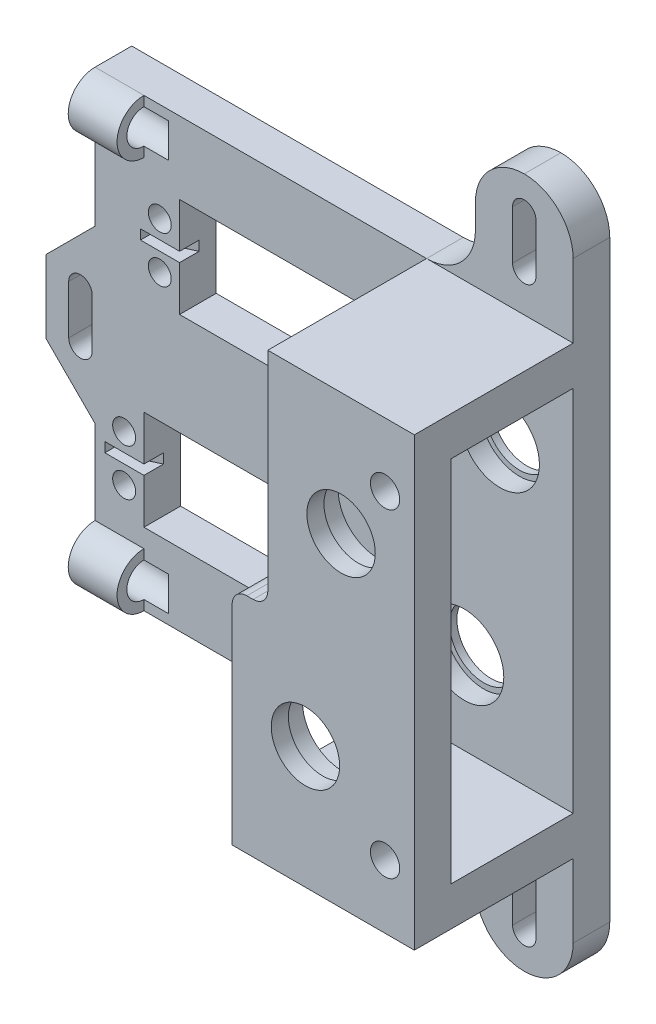
SolidWorks part; units mm, degrees
ref_plane "Front Plane" through (0, 0, 0) normal (0, 0, 1) x (1, 0, 0)
ref_plane "Top Plane" through (0, 0, 0) normal (0, 1, 0) x (1, 0, 0)
ref_plane "Right Plane" through (0, 0, 0) normal (1, 0, 0) x (0, 0, -1)
sketch "Sketch1" plane through (0, 0, 0) normal (0, 0, 1) x (1, 0, 0)
  line L0 (-15, 0) -> (22.2932, 0)
  line L5 (-15, 91.3619) -> (22.2932, 91.3619)
  line L6 (-15, 0) -> (-15, 91.3619)
  line L7 (22.2932, 0) -> (22.2932, 91.3619)
  line L8 (0, 25) -> (7.2932, 66.3619) construction
  line L9 (0, 25) -> (0, 79.2) construction
  circle A1 centre (0, 25) radius 8.1
  circle A2 centre (7.2932, 66.3619) radius 8.1
  point P4 (0, 0)
  dimension "D2" = 16.2
  dimension "D5" = 25
  dimension "D4" = 15
  dimension "D6" = 25
  dimension "D8" = 42
  dimension "D9" = 10
  dimension "D10" = 15
extrude "Boss-Extrude1" add sketch "Sketch1" along normal blind 40
ref_plane "INNER WALL" through (0, 0, 39) normal (0, 0, 1) x (1, 0, 0)
ref_plane "OUTER WALL" through (0, 0, 32.65) normal (0, 0, 1) x (1, 0, 0)
sketch "Sketch2" plane through (0, 0, 0) normal (0, 1, 0) x (1, 0, 0)
  line L1 (-15, -7.5) -> (22.2932, -7.5)
  line L2 (-15, -7.5) -> (-15, -32.5)
  line L3 (-15, -32.5) -> (22.2932, -32.5)
  line L4 (22.2932, -7.5) -> (22.2932, -32.5)
  line L6 (-15, -40) -> (-15, 0) construction
  line L7 (22.2932, -40) -> (22.2932, 0) construction
  point P9 (22.2932, -20)
  point P10 (22.2932, -20)
  dimension "D1" = 25
extrude "Cut-Extrude1" cut sketch "Sketch2" along normal through all from offset 8
sketch "Sketch10" plane through (0, 0, 40) normal (0, 0, 1) x (1, 0, 0)
  circle A0 centre (7.2932, 66.3619) radius 8.1
  circle A1 centre (0, 25) radius 10.837
  circle A2 centre (7.2932, 66.3619) radius 7
  circle A3 centre (0, 25) radius 7
  circle A4 centre (7.2932, 66.3619) radius 8.1 construction
  circle A5 centre (0, 25) radius 8.1 construction
  dimension "D2" = 14
  dimension "D4" = 14
extrude "Boss-Extrude2" add sketch "Sketch10" against normal offset from surface (3.5 mm away) 4 up to face at (-8.1, 25, 32.5)
sketch "Sketch11" plane through (0, 0, 0) normal (0, 0, -1) x (-1, 0, 0)
  circle A0 centre (-7.2932, 66.3619) radius 8.1
  circle A1 centre (-7.2932, 66.3619) radius 7
  circle A2 centre (0, 25) radius 8.1
  circle A3 centre (0, 25) radius 7
  circle A4 centre (0, 25) radius 8.1 construction
  circle A5 centre (-7.2932, 66.3619) radius 8.1 construction
  dimension "D1" = 14
  dimension "D2" = 14
extrude "Boss-Extrude3" add sketch "Sketch11" against normal offset from surface (3.5 mm away) 4 up to face at (8.1, 25, 7.5)
ref_axis "Axis1" through (0, 25, 3.5) along (0, 0, -1)
ref_plane "Plane1" through (0, 25, 0) normal (0, -1, 0) x (-1, 0, 0)
ref_axis "Axis2" through (7.2932, 66.3619, 3.5) along (0, 0, -1)
ref_plane "Plane2" through (0, 66.3619, 0) normal (0, -1, 0) x (-1, 0, 0)
sketch "Sketch12" plane through (0, 0, 0) normal (0, 0, -1) x (-1, 0, 0)
  line L0 (-20.5113, 25) -> (20.5113, 25) construction
  line L1 (15, 0) -> (75.56, 0)
  line L2 (15, 0) -> (15, 91.3619)
  line L3 (15, 91.3619) -> (75.56, 91.3619)
  line L5 (-20.5113, 66.3619) -> (20.5113, 66.3619) construction
  line L6 (24.66, 35.2) -> (65.56, 35.2)
  line L7 (24.66, 35.2) -> (24.66, 14.8)
  line L8 (24.66, 14.8) -> (65.56, 14.8)
  line L9 (65.56, 35.2) -> (65.56, 14.8)
  line L10 (-22.2932, 91.3619) -> (15, 91.3619) construction
  line L11 (17.3668, 76.5619) -> (58.2668, 76.5619)
  line L12 (17.3668, 76.5619) -> (17.3668, 56.1619)
  line L13 (17.3668, 56.1619) -> (58.2668, 56.1619)
  line L14 (58.2668, 76.5619) -> (58.2668, 56.1619)
  line L16 (15, 0) -> (-22.2932, 0) construction
  line L17 (15, 91.3619) -> (15, 0) construction
  line L20 (75.56, 91.3619) -> (75.56, 0)
  line L21 (58.2668, 56.1619) -> (58.2668, 35.2) construction
  line L22 (45.11, 35.2) -> (45.11, 14.8) construction
  line L32 (37.8168, 76.5619) -> (37.8168, 56.1619) construction
  circle A0 centre (35, 25) radius 6.6 construction
  circle A1 centre (0, 25) radius 7 construction
  circle A2 centre (27.7068, 66.3619) radius 6.6 construction
  circle A3 centre (-7.2932, 66.3619) radius 7 construction
  point P15 (45.11, 14.8)
  point P27 (17.3668, 66.3619)
  point P34 (37.8168, 56.1619)
  point P53 (45.11, 25)
  dimension "D7" = 13.2
  dimension "D11" = 13.2
  dimension "D2" = 20.4
  dimension "D3" = 40.9
  dimension "D4" = 10.11
  dimension "D9" = 10.11
  dimension "D5" = 35
  dimension "D6" = 10
extrude "Boss-Extrude4" add sketch "Sketch12" against normal up to surface (7.5 mm away) up to face at (8.1, 25, 7.5)
sketch "Sketch13" plane through (0, 0, 0) normal (0, 0, -1) x (-1, 0, 0)
  line L0 (24.66, 35.2) -> (24.66, 14.8) construction
  line L1 (-20.5113, 25) -> (20.5113, 25) construction
  line L2 (65.56, 14.8) -> (65.56, 35.2) construction
  line L3 (17.3668, 76.5619) -> (17.3668, 56.1619) construction
  line L5 (-20.5113, 66.3619) -> (20.5113, 66.3619) construction
  line L6 (58.2668, 56.1619) -> (58.2668, 76.5619) construction
  circle A0 centre (20.61, 29.75) radius 2.3495
  circle A1 centre (20.61, 20.25) radius 2.3495
  circle A2 centre (69.61, 29.75) radius 2.3495
  circle A3 centre (69.61, 20.25) radius 2.3495
  circle A4 centre (13.3168, 71.1119) radius 2.3495
  circle A5 centre (13.3168, 61.6119) radius 2.3495
  circle A6 centre (62.3168, 71.1119) radius 2.3495
  circle A7 centre (62.3168, 61.6119) radius 2.3495
  dimension "D1" = 4.699
  dimension "D2" = 4.05
  dimension "D3" = 9.5
  dimension "D4" = 4.75
  dimension "D5" = 4.05
  dimension "D7" = 9.5
  dimension "D8" = 4.05
  dimension "D9" = 4.75
  dimension "D10" = 4.05
extrude "Cut-Extrude2" cut sketch "Sketch13" against normal up to next
sketch "Sketch22" plane through (0, 0, 7.5) normal (0, 0, 1) x (1, 0, 0)
  line L0 (-58.2668, 56.1619) -> (-58.2668, 76.5619) construction
  line L1 (-58.2668, 65.3619) -> (-66.2668, 65.3619)
  line L2 (-58.2668, 65.3619) -> (-58.2668, 67.3619)
  line L3 (-58.2668, 67.3619) -> (-66.2668, 67.3619)
  line L4 (-66.2668, 65.3619) -> (-66.2668, 67.3619)
  line L5 (-17.3668, 76.5619) -> (-17.3668, 56.1619) construction
  line L6 (-17.3668, 65.3619) -> (-9.3668, 65.3619)
  line L7 (-17.3668, 65.3619) -> (-17.3668, 67.3619)
  line L8 (-17.3668, 67.3619) -> (-9.3668, 67.3619)
  line L9 (-9.3668, 65.3619) -> (-9.3668, 67.3619)
  line L10 (-24.66, 35.2) -> (-24.66, 14.8) construction
  line L11 (-24.66, 24) -> (-16.66, 24)
  line L12 (-24.66, 24) -> (-24.66, 26)
  line L13 (-24.66, 26) -> (-16.66, 26)
  line L14 (-16.66, 24) -> (-16.66, 26)
  line L15 (-65.56, 14.8) -> (-65.56, 35.2) construction
  line L16 (-65.56, 24) -> (-73.56, 24)
  line L17 (-65.56, 24) -> (-65.56, 26)
  line L18 (-65.56, 26) -> (-73.56, 26)
  line L19 (-73.56, 24) -> (-73.56, 26)
  point P24 (-58.2668, 66.3619)
  point P25 (-66.2668, 66.3619)
  point P26 (-73.56, 25)
  point P27 (-65.56, 25)
  dimension "D1" = 2
  dimension "D2" = 8
extrude "Cut-Extrude6" cut sketch "Sketch22" against normal blind 2
sketch "Sketch14" plane through (0, 0, 7.5) normal (0, 0, 1) x (1, 0, 0)
  line L0 (22.2932, 0) -> (22.2932, 91.3619) construction
  line L1 (22.2932, 91.3619) -> (-15, 91.3619)
  line L2 (22.2932, 91.3619) -> (22.2932, 83.3619)
  line L3 (22.2932, 83.3619) -> (-15, 83.3619)
  line L4 (-15, 91.3619) -> (-15, 83.3619)
  line L5 (22.2932, 91.3619) -> (-15, 91.3619) construction
  line L6 (-15, 91.3619) -> (-15, 0) construction
  dimension "D1" = 8
extrude "Boss-Extrude5" add sketch "Sketch14" along normal up to surface (25 mm away) up to face at (-8.1, 25, 32.5)
sketch "Sketch18" plane through (0, 0, 40) normal (0, 0, 1) x (1, 0, 0)
  line L0 (7.2932, 66.3619) -> (7.2932, 25) construction
  line L1 (-15, 91.3619) -> (-7.7068, 91.3619)
  line L2 (-15, 91.3619) -> (-15, 45.681)
  line L3 (-15, 45.681) -> (-7.7068, 45.681)
  line L4 (-7.7068, 91.3619) -> (-7.7068, 45.681)
  line L5 (0, 25) -> (7.2932, 25) construction
  circle A0 centre (7.2932, 66.3619) radius 8.1 construction
  point P13 (7.2932, 45.681)
  dimension "D1" = 15
extrude "Cut-Extrude4" cut sketch "Sketch18" against normal up to surface (32.5 mm away) up to face at (-45.11, 25, 7.5)
sketch "Sketch15" plane through (0, 0, 0) normal (0, 0, -1) x (-1, 0, 0)
  circle A0 centre (0, 25) radius 11
  circle A1 centre (-7.2932, 66.3619) radius 11
  dimension "D1" = 22
extrude "Cut-Extrude3" cut sketch "Sketch15" against normal blind 2
chamfer "Chamfer2" distance 2 angle 65 4 edges at (-65.56, 25, 5.5) (-58.2668, 66.3619, 5.5) (-17.3668, 66.3619, 5.5) (-24.66, 25, 5.5) first distance on face at (-65.56, 25, 5.125) first distance on face at (-58.2668, 66.3619, 5.125) first distance on face at (-17.3668, 66.3619, 5.125) first distance on face at (-24.66, 25, 5.125)
sketch "Sketch23" plane through (0, 0, 7.5) normal (0, 0, 1) x (1, 0, 0)
  line L0 (-15, 0) -> (22.2932, 0) construction
  line L1 (2.2932, 0) -> (22.2932, 0)
  line L2 (2.2932, 0) -> (2.2932, -25)
  line L3 (2.2932, -25) -> (22.2932, -25)
  line L4 (22.2932, 0) -> (22.2932, -25)
  line L5 (22.2932, 0) -> (22.2932, 91.3619) construction
  line L6 (22.2932, 91.3619) -> (2.2932, 91.3619)
  line L7 (22.2932, 91.3619) -> (22.2932, 116.3619)
  line L8 (22.2932, 116.3619) -> (2.2932, 116.3619)
  line L9 (2.2932, 91.3619) -> (2.2932, 116.3619)
  line L10 (-75.56, 0) -> (-75.56, 91.3619) construction
  line L11 (-75.56, 38.181) -> (-85.56, 38.181)
  line L12 (-75.56, 38.181) -> (-75.56, 53.181)
  line L13 (-75.56, 53.181) -> (-85.56, 53.181)
  line L14 (-85.56, 38.181) -> (-85.56, 53.181)
  point P19 (-75.56, 45.681)
  point P20 (-85.56, 45.681)
  dimension "D1" = 20
  dimension "D2" = 25
  dimension "D3" = 15
  dimension "D4" = 10
extrude "Boss-Extrude6" add sketch "Sketch23" against normal up to surface (7.5 mm away) up to face at (-11, 25, 0)
fillet "Fillet1" radius 10 6 edges at (2.2932, 116.3619, 3.75) (22.2932, 116.3619, 3.75) (22.2932, -25, 3.75) (2.2932, -25, 3.75) (2.2932, 0, 3.75) (2.2932, 91.3619, 3.75)
chamfer "Chamfer3" distance 10 angle 45 2 edges at (-75.56, 38.181, 3.75) (-75.56, 53.181, 3.75)
sketch "Sketch26" plane through (0, 0, 40) normal (0, 0, 1) x (1, 0, 0)
  line L0 (22.2932, 0) -> (22.2932, 91.3619) construction
  line L1 (22.2932, 91.3619) -> (-7.7068, 91.3619) construction
  line L2 (-15, 0) -> (22.2932, 0) construction
  circle A0 centre (16.2932, 78.3619) radius 3
  circle A1 centre (16.2932, 13) radius 3
  point P10 (0, 0)
  dimension "D1" = 6
  dimension "D2" = 6
  dimension "D3" = 6
  dimension "D4" = 13
  dimension "D5" = 13
extrude "Cut-Extrude7" cut sketch "Sketch26" against normal up to next
sketch "Sketch24" plane through (0, 0, 7.5) normal (0, 0, 1) x (1, 0, 0)
  line L0 (-85.56, 53.181) -> (-85.56, 38.181) construction
  point P0 (12.2932, 109.3619)
  point P3 (12.2932, -18)
  point P6 (-78.56, 45.681)
  point P20 (-85.56, 45.681)
  dimension "D1" = 7
  dimension "D2" = 7
  dimension "D3" = 7
hole_wizard "M4 Clearance Hole1" positions "Sketch24" profile "Sketch25" hole size "M4" standard "ANSI Metric" end condition through all
sketch "Sketch25" plane through (12.2932, 109.3619, 7.5) normal (1, 0, 0) x (0, -1, 0)
  line L0 (0, 0) -> (0, 7.5)
  line L1 (0, 7.5) -> (2.4, 7.5)
  line L2 (2.4, 7.5) -> (2.4, 0)
  line L5 (2.4, 0) -> (0, 0)
  line L11 (0, -6.35) -> (0, 107.95) construction
  dimension "Thru Hole Dia." = 4.8
  dimension "Thru Hole Depth" = 7.5
sketch "Sketch27" plane through (0, 0, 7.5) normal (0, 0, 1) x (1, 0, 0)
  line L0 (12.2932, 109.3619) -> (12.2932, 99.3619) construction
  line L1 (14.6932, 109.3619) -> (14.6932, 99.3619)
  line L2 (9.8932, 109.3619) -> (9.8932, 99.3619)
  line L3 (12.2932, -18) -> (12.2932, -8) construction
  line L4 (9.8932, -18) -> (9.8932, -8)
  line L5 (14.6932, -18) -> (14.6932, -8)
  line L6 (-78.56, 40.681) -> (-78.56, 50.681) construction
  line L7 (-80.96, 40.681) -> (-80.96, 50.681)
  line L8 (-76.16, 40.681) -> (-76.16, 50.681)
  arc A0 (14.6932, 109.3619) -> (9.8932, 109.3619) centre (12.2932, 109.3619) ccw
  arc A1 (9.8932, 99.3619) -> (14.6932, 99.3619) centre (12.2932, 99.3619) ccw
  arc A2 (9.8932, -18) -> (14.6932, -18) centre (12.2932, -18) ccw
  arc A3 (14.6932, -8) -> (9.8932, -8) centre (12.2932, -8) ccw
  circle A4 centre (12.2932, -18) radius 2.4 construction
  circle A5 centre (12.2932, 109.3619) radius 2.4 construction
  arc A6 (-80.96, 40.681) -> (-76.16, 40.681) centre (-78.56, 40.681) ccw
  arc A7 (-76.16, 50.681) -> (-80.96, 50.681) centre (-78.56, 50.681) ccw
  circle A8 centre (-78.56, 45.681) radius 2.4 construction
  point P3 (12.2932, 104.3619)
  point P8 (12.2932, -13)
  point P22 (-78.56, 45.681)
  dimension "D1" = 10
  dimension "D2" = 10
  dimension "D3" = 10
extrude "Cut-Extrude8" cut sketch "Sketch27" against normal through all
sketch "Sketch28" plane through (-75.56, 0, 0) normal (-1, 0, 0) x (0, 0, 1)
  line L0 (7.5, 63.181) -> (7.5, 91.3619) construction
  line L1 (7.5, 0) -> (7.5, 28.181) construction
  line L2 (7.5, 91.3619) -> (7.5, 83.3619) construction
  line L3 (7.5, 82.3619) -> (7.5, 80.3619)
  line L4 (7.5, 89.3619) -> (7.5, 91.3619)
  line L5 (7.5, 11) -> (7.5, 9)
  line L6 (7.5, 2) -> (7.5, 0)
  line L7 (7.5, 8) -> (7.5, 0) construction
  arc A0 (7.5, 91.3619) -> (7.5, 80.3619) centre (7.5, 85.8619) cw
  arc A1 (7.5, 0) -> (7.5, 11) centre (7.5, 5.5) ccw
  arc A2 (7.5, 9) -> (7.5, 2) centre (7.5, 5.5) cw
  arc A3 (7.5, 82.3619) -> (7.5, 89.3619) centre (7.5, 85.8619) ccw
  point P18 (7.5, 63.398)
  point P21 (7.5, 86.2738)
  dimension "D2" = 3.5
  dimension "D1" = 2
extrude "Boss-Extrude7" add sketch "Sketch28" against normal blind 10
sketch "Sketch29" plane through (-75.56, 0, 0) normal (-1, 0, 0) x (0, 0, 1)
  line L0 (7.5, 82.3619) -> (7.5, 89.3619) construction
  line L1 (7.5, 2) -> (7.5, 9) construction
  circle A0 centre (7.5, 85.8619) radius 3.5
  circle A1 centre (7.5, 5.5) radius 3.5
  arc A2 (7.5, 82.3619) -> (7.5, 89.3619) centre (7.5, 85.8619) ccw construction
  arc A3 (7.5, 2) -> (7.5, 9) centre (7.5, 5.5) ccw construction
  point P14 (7.5, 86.3619)
extrude "Cut-Extrude9" cut sketch "Sketch29" against normal up to surface (10 mm away) up to face at (-65.56, 85.8619, 9.75)
chamfer "Chamfer4" distance 5 angle 45 2 edges at (-65.56, 85.8619, 7.5) (-65.56, 5.5, 7.5)
fillet "Fillet3" radius 3 2 edges at (-15, 45.681, 36.25) (-7.7068, 45.681, 36.25)
equation "\"D4@Sketch13\"=\"D3@Sketch13\"/2"
equation "\"D5@Sketch12\"=\"D1@Sketch12\""
equation "\"D8@Sketch13\"=\"D2@Sketch13\""
equation "\"D9@Sketch13\"=\"D7@Sketch13\"/2"
equation "\"D10@Sketch13\"=\"D5@Sketch13\""
